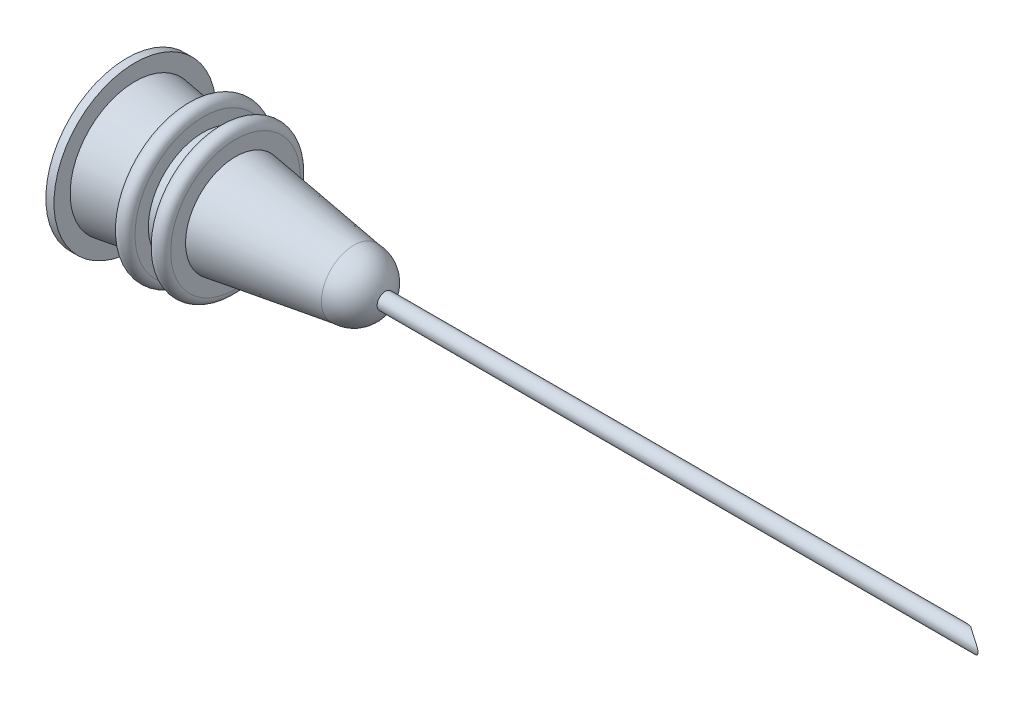
SolidWorks part; units mm, degrees
ref_plane "Front Plane" through (0, 0, 0) normal (0, 0, 1) x (1, 0, 0)
ref_plane "Top Plane" through (0, 0, 0) normal (0, 1, 0) x (1, 0, 0)
ref_plane "Right Plane" through (0, 0, 0) normal (1, 0, 0) x (0, 0, -1)
sketch "Sketch1" plane through (0, 0, 0) normal (0, 0, 1) x (1, 0, 0)
  line L0 (0, 0) -> (-12.1986, 0) construction
  line L1 (0, 0) -> (0, 2)
  line L2 (0, 2) -> (-7.3, 3.0815)
  line L3 (-13.5, 4) -> (-13.5, 5)
  line L4 (-13.5, 5) -> (-14, 5)
  line L5 (-14, 5) -> (-14, 3.3159)
  line L6 (-14, 3.3159) -> (-1, 1.39)
  line L7 (-1, 1.39) -> (-1, 0)
  line L8 (-1, 0) -> (0, 0)
  line L9 (-7.3, 4) -> (-7.3, 3.0815)
  line L10 (-8.3, 4) -> (-8.3, 3.2296)
  line L11 (-9.3, 4.2) -> (-9.3, 3.3778)
  line L12 (-10.3, 4.2) -> (-10.3, 3.5259)
  line L13 (-10.3, 3.5259) -> (-13.5, 4)
  line L14 (-8.3, 3.2296) -> (-9.3, 3.3778)
  arc A0 (-7.3, 4) -> (-8.3, 4) centre (-7.8, 4) ccw
  arc A1 (-9.3, 4.2) -> (-10.3, 4.2) centre (-9.8, 4.2) ccw
  dimension "D10" = 1
  dimension "D11" = 1
  dimension "D1" = 1
  dimension "D2" = 0.75
  dimension "D3" = 0.5
  dimension "D4" = 2
  dimension "D5" = 5
  dimension "D6" = 4
  dimension "D7" = 4
  dimension "D8" = 4.2
  dimension "D9" = 2
  dimension "D12" = 14
  dimension "D13" = 7.8
revolve "Revolve1" add sketch "Sketch1" angle 360 about L0
dome "Dome1" faces to dome 1 distance 2 reverse direction no elliptical dome no face at (0, 0, -2) parameters "D1"=2
sketch "Sketch2" plane through (-1, 0, 0) normal (-1, 0, 0) x (0, 0, 1)
  circle A0 centre (0, 0) radius 0.5
  dimension "D1" = 1
extrude "Cut-Extrude1" cut sketch "Sketch2" against normal through all
sketch "Sketch3" plane through (-1, 0, 0) normal (-1, 0, 0) x (0, 0, 1)
  circle A0 centre (0, 0) radius 0.5 construction
  circle A1 centre (0, 0) radius 0.5
extrude "Extrude-Thin1" add sketch "Sketch3" against normal blind 40 thin thin type one direction reverse wall 0.125
sketch "Sketch4" plane through (0, 0, 0) normal (0, 1, 0) x (1, 0, 0)
  line L0 (39, 0) -> (39, 3.5) construction
  line L1 (39, -0.5) -> (39, 0.5) construction
  circle A1 centre (39, 3.5) radius 3.5
  dimension "D1" = 3.5
extrude "Cut-Extrude2" cut sketch "Sketch4" against normal through all both and the other way through all
sketch "Sketch6" plane through (0, 0, 0) normal (0, 1, 0) x (1, 0, 0)
  line L0 (39, -0.5) -> (41, -0.5) construction
  line L1 (41, -0.5) -> (41, 4.0826) construction
  circle A0 centre (41, 4.0826) radius 5
  dimension "D2" = 10
  dimension "D1" = 2
extrude "Cut-Extrude3" cut sketch "Sketch6" against normal through all both and the other way through all
